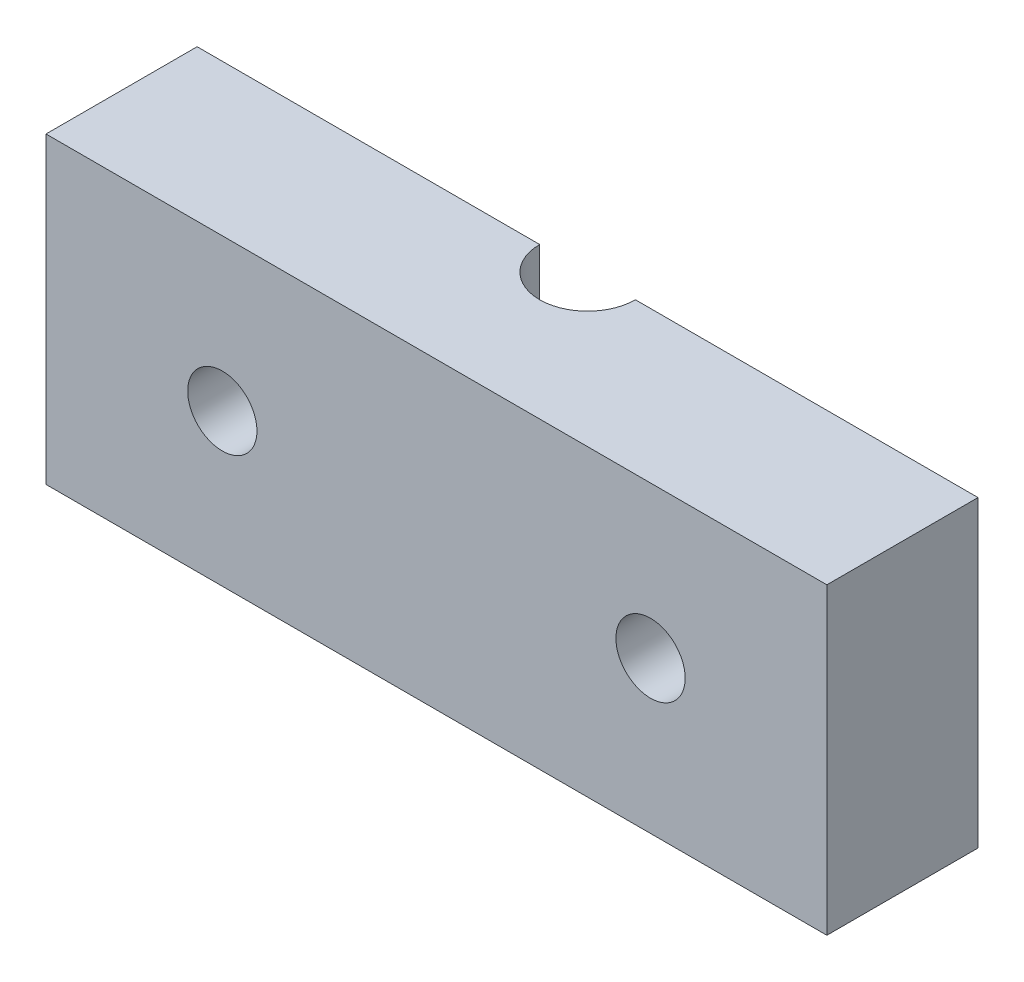
SolidWorks part; units mm, degrees
ref_plane "Front Plane" through (0, 0, 0) normal (0, 0, 1) x (1, 0, 0)
ref_plane "Top Plane" through (0, 0, 0) normal (0, 1, 0) x (1, 0, 0)
ref_plane "Right Plane" through (0, 0, 0) normal (1, 0, 0) x (0, 0, -1)
sketch "Sketch1" plane through (0, 0, 0) normal (0, 0, 1) x (1, 0, 0)
  line L0 (-15.5, 0) -> (15.5, 0) construction
  line L1 (-15.5, 6.025) -> (15.5, 6.025)
  line L2 (-15.5, 6.025) -> (-15.5, -6.025)
  line L3 (-15.5, -6.025) -> (15.5, -6.025)
  line L4 (15.5, 6.025) -> (15.5, -6.025)
  line L5 (-15.5, 6.025) -> (15.5, -6.025) construction
  line L6 (-15.5, -6.025) -> (15.5, 6.025) construction
  circle A0 centre (-8.5, 0) radius 1.375
  circle A1 centre (8.5, 0) radius 1.375
  point P0 (0, 0)
  dimension "D3" = 2.75
  dimension "D4" = 17
  dimension "D5" = 7
  dimension "D1" = 12.05
  dimension "D2" = 31
extrude "Base" add sketch "Sketch1" along normal blind 6
sketch "Sketch2" plane through (0, 6.025, 0) normal (0, 1, 0) x (1, 0, 0)
  line L0 (15.5, 0) -> (-15.5, 0) construction
  line L1 (-1.9, 0) -> (1.9, 0)
  arc A0 (-1.9, 0) -> (1.9, 0) centre (0, 0) ccw
  dimension "D1" = 1.9
extrude "Wire Grove" cut sketch "Sketch2" against normal through all
